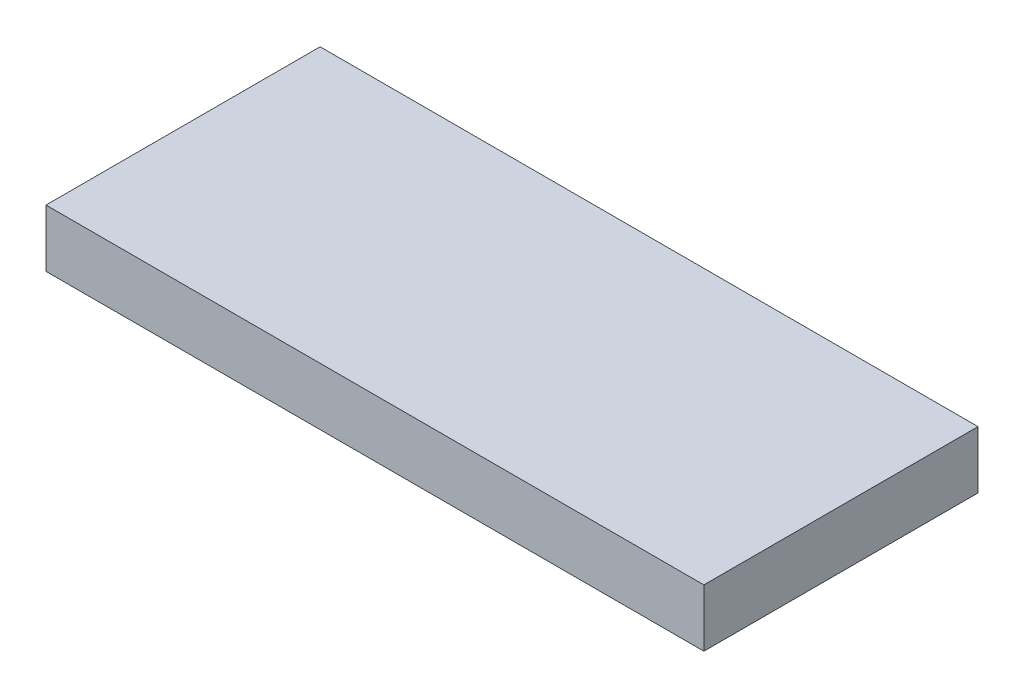
SolidWorks part; units mm, degrees
ref_plane "Front Plane" through (0, 0, 0) normal (0, 0, 1) x (1, 0, 0)
ref_plane "Top Plane" through (0, 0, 0) normal (0, 1, 0) x (1, 0, 0)
ref_plane "Right Plane" through (0, 0, 0) normal (1, 0, 0) x (0, 0, -1)
sketch "Sketch1" plane through (0, 0, 0) normal (0, 1, 0) x (1, 0, 0)
  line L1 (0, 0) -> (76.2, 0)
  line L2 (0, 0) -> (0, 31.75)
  line L3 (0, 31.75) -> (76.2, 31.75)
  line L4 (76.2, 0) -> (76.2, 31.75)
  dimension "D1" = 76.2
  dimension "D2" = 31.75
extrude "Boss-Extrude1" add sketch "Sketch1" along normal blind 6.6548
